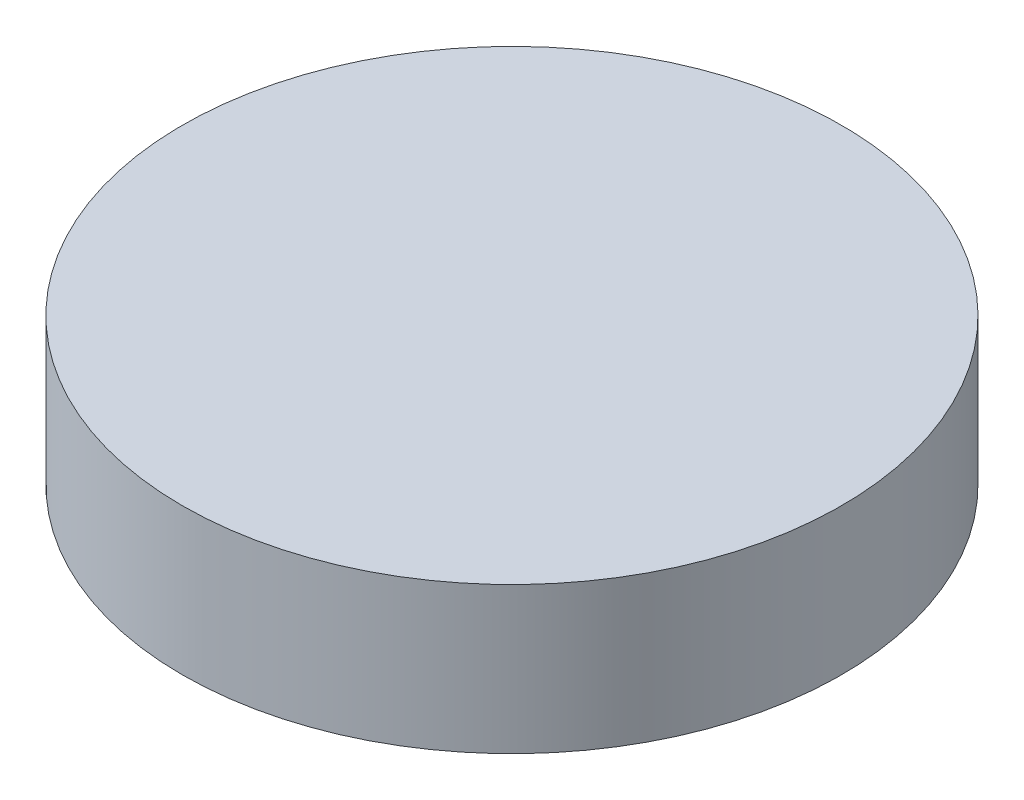
SolidWorks part; units mm, degrees
ref_plane "Front Plane" through (0, 0, 0) normal (0, 0, 1) x (1, 0, 0)
ref_plane "Top Plane" through (0, 0, 0) normal (0, 1, 0) x (1, 0, 0)
ref_plane "Right Plane" through (0, 0, 0) normal (1, 0, 0) x (0, 0, -1)
sketch "Sketch1" plane through (0, 0, 0) normal (0, 1, 0) x (1, 0, 0)
  circle A0 centre (0, 0) radius 22.5
  dimension "D1" = 45
extrude "Boss-Extrude1" add sketch "Sketch1" along normal blind 5 and the other way blind 5
